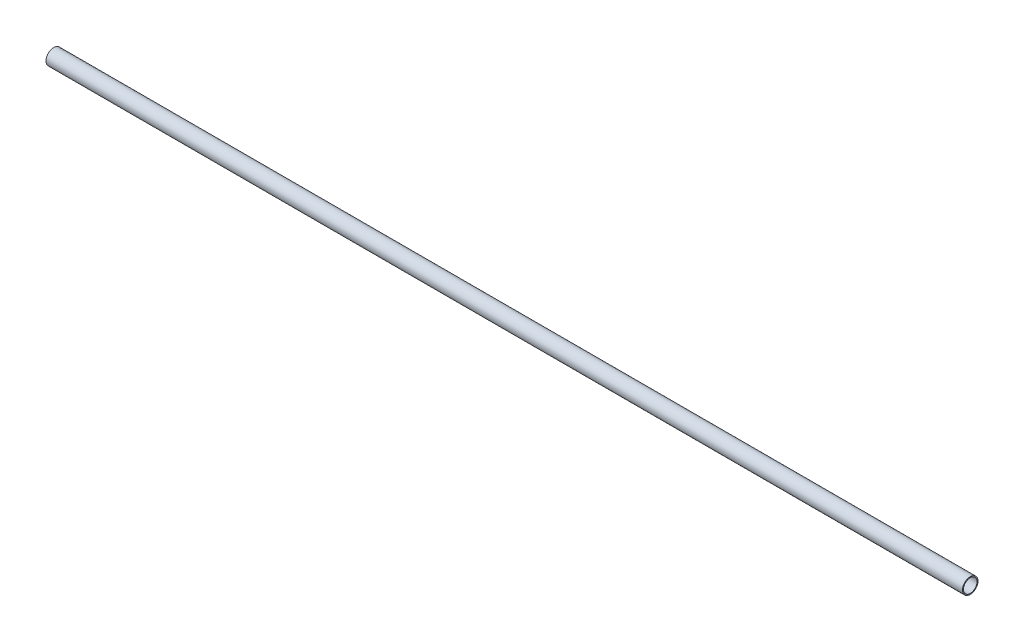
SolidWorks part; units mm, degrees
ref_plane "Front Plane" through (0, 0, 0) normal (0, 0, 1) x (1, 0, 0)
ref_plane "Top Plane" through (0, 0, 0) normal (0, 1, 0) x (1, 0, 0)
ref_plane "Right Plane" through (0, 0, 0) normal (1, 0, 0) x (0, 0, -1)
sketch "Sketch1" plane through (0, 0, 0) normal (1, 0, 0) x (0, 0, -1)
  circle A0 centre (0, 0) radius 12.7
  circle A1 centre (0, 0) radius 11.1125
  dimension "D1" = 25.4
  dimension "D2" = 22.225
extrude "Boss-Extrude1" add sketch "Sketch1" along normal blind 749.3 and the other way blind 749.3 contours A0 A1 region at (0, 0, 12.3408)
